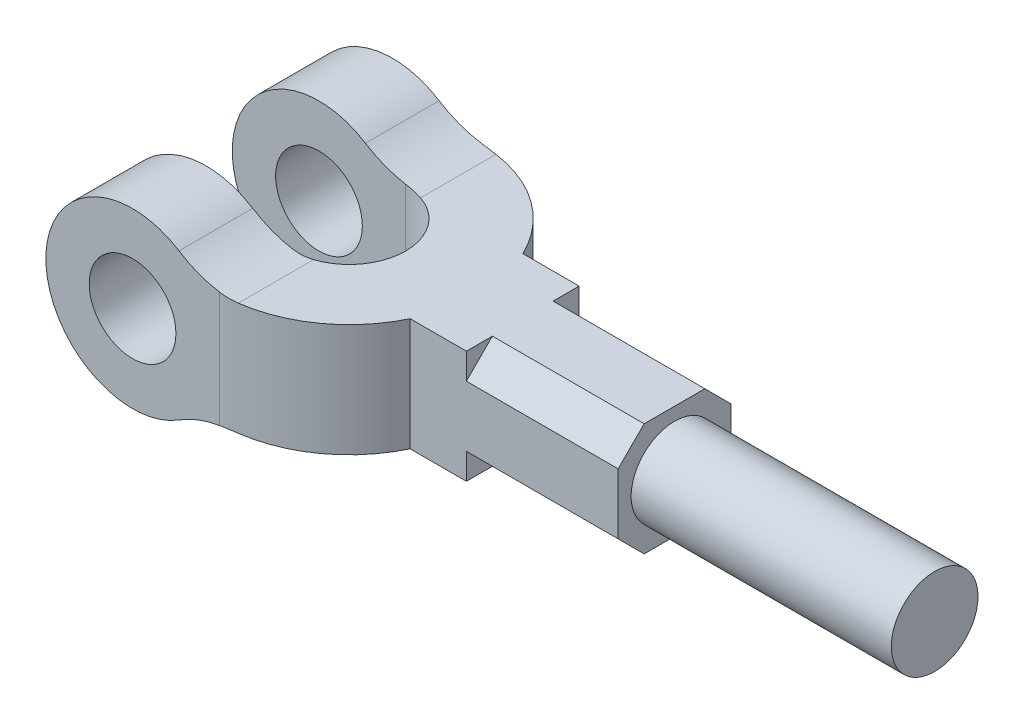
SolidWorks part; units mm, degrees
ref_plane "Front Plane" through (0, 0, 0) normal (0, 0, 1) x (1, 0, 0)
ref_plane "Top Plane" through (0, 0, 0) normal (0, 1, 0) x (1, 0, 0)
ref_plane "Right Plane" through (0, 0, 0) normal (1, 0, 0) x (0, 0, -1)
sketch "Sketch1" plane through (0, 0, 0) normal (0, 1, 0) x (1, 0, 0)
  line L1 (-57.5, 30) -> (57.5, 30)
  line L2 (-57.5, 30) -> (-57.5, -30)
  line L3 (-57.5, -30) -> (57.5, -30)
  line L4 (57.5, 30) -> (57.5, -30)
  line L5 (-57.5, 30) -> (57.5, -30) construction
  line L6 (-57.5, -30) -> (57.5, 30) construction
  point P0 (0, 0)
  dimension "D1" = 60
  dimension "D2" = 115
extrude "Boss-Extrude1" add sketch "Sketch1" along normal blind 40
sketch "Sketch2" plane through (0, 40, 0) normal (0, 1, 0) x (1, 0, 0)
  line L0 (-57.5, 0) -> (15.5, 0) construction
  line L1 (-57.5, 0) -> (52.37, 0) construction
  line L3 (-57.5, 13) -> (-17.5, 13)
  line L6 (-57.5, -30) -> (-17.5, -30)
  line L7 (-57.5, -13) -> (-57.5, -30)
  line L9 (-57.5, 13) -> (52.37, 13) construction
  line L10 (-57.5, 13) -> (-57.5, 30)
  line L11 (-57.5, 30) -> (-17.5, 30)
  line L15 (57.5, 30) -> (-57.5, 30) construction
  line L17 (-57.5, 30) -> (-57.5, -30) construction
  line L18 (-57.5, -13) -> (-17.5, -13)
  line L19 (9.537, -13) -> (57.5, -13)
  line L20 (57.5, -30) -> (57.5, 30) construction
  line L21 (57.5, -13) -> (57.5, 13)
  line L22 (57.5, 13) -> (9.537, 13)
  arc A4 (-17.5, -13) -> (-17.5, 13) centre (-17.5, 0) ccw
  arc A5 (-17.5, -30) -> (9.537, -13) centre (-17.5, 0) ccw
  arc A6 (9.537, 13) -> (-17.5, 30) centre (-17.5, 0) ccw
  line M12 (57.5, -30) -> (57.5, 30)
  line M13 (57.5, 30) -> (-57.5, 30)
  line M14 (-57.5, 30) -> (-57.5, -30)
  line M15 (-57.5, -30) -> (57.5, -30)
  dimension "D4" = 40
  dimension "D3" = 40
  dimension "D1" = 13
  dimension "D2" = 13
extrude "Cut-Extrude1" cut sketch "Sketch2" against normal blind 40 contours L18 A4 L3 M14 | A6 L22 M12 M13 | A5 L19 M15 M12 region at (-32.3111, 40, 0) region at (29.3463, 40, -22.0233) region at (29.3463, 40, 22.0233)
sketch "Sketch3" plane through (0, 0, 30) normal (0, 0, 1) x (1, 0, 0)
  line L0 (57.5, 0) -> (57.5, 40) construction
  line L1 (-57.5, 40) -> (-17.5, 40) construction
  line L2 (-37.5, 20) -> (57.5, 20) construction
  line L3 (-13.3961, 7) -> (57.5, 7)
  line L4 (-13.3961, 33) -> (57.5, 33)
  line L5 (-37.5, 33) -> (57.5, 33) construction
  line L6 (-37.5, 7) -> (57.5, 7) construction
  line L7 (57.5, 33) -> (57.5, 7)
  line L8 (9.537, 0) -> (57.5, 0) construction
  line L9 (-17.5, 0) -> (9.537, 0) construction
  line L10 (-57.5, 0) -> (-17.5, 0) construction
  line L11 (9.537, 40) -> (-17.5, 40) construction
  line L12 (9.537, 40) -> (57.5, 40) construction
  line L13 (9.537, 0) -> (57.5, 0)
  line L14 (-17.5, 0) -> (9.537, 0)
  line L15 (-57.5, 0) -> (-17.5, 0)
  line L16 (-57.5, 40) -> (-17.5, 40)
  line L17 (9.537, 40) -> (-17.5, 40)
  line L18 (9.537, 40) -> (57.5, 40)
  line L19 (57.5, 0) -> (57.5, 40)
  arc A0 (-26.7871, 36.8889) -> (-26.7871, 3.1111) centre (-37.5, 20) ccw
  circle A1 centre (-37.5, 20) radius 10
  arc A2 (-13.3961, 33) -> (-26.7871, 36.8889) centre (-13.3961, 58) cw
  arc A3 (-13.3961, 7) -> (-26.7871, 3.1111) centre (-13.3961, -18) ccw
  line M4 (-57.5, 0) -> (-17.5, 0)
  line M5 (-17.5, 0) -> (-17.5, 40)
  line M6 (-17.5, 40) -> (-57.5, 40)
  line M7 (-57.5, 40) -> (-57.5, 0)
  dimension "D1" = 40
  dimension "D2" = 20
  dimension "D7" = 25
  dimension "D3" = 95
  dimension "D4" = 20
  dimension "D5" = 13
  dimension "D6" = 13
extrude "Cut-Extrude3" cut sketch "Sketch3" against normal blind 98 contours A0 L16 M7 | A0 M7 M4 | A2 A0 M5 M6 | A2 L4 L19 L18 L17 M5 | L3 A3 L14 L13 L19 M5 | A3 A0 L15 M5 region at (20.0322, 3.497, 30) region at (-23.0334, 2.3964, 30) region at (20.0322, 36.503, 30) region at (-23.0334, 37.6036, 30) region at (-53.0326, 4.4674, 30) region at (-53.0326, 35.5326, 30)
extrude "Cut-Extrude4" cut sketch "Sketch3<4>" against normal blind 98 contours A1 region at (-37.5, 20, 30)
sketch "Sketch3<4>" plane through (0, 0, 30) normal (0, 0, 1) x (1, 0, 0) same geometry as "Sketch3"
sketch "Sketch4" plane through (57.5, 0, 0) normal (1, 0, 0) x (0, 0, -1)
  line L0 (13, 7) -> (-13, 7) construction
  line L1 (13, 7) -> (13, 33) construction
  line L2 (-13, 33) -> (-13, 27)
  line L3 (-12.3352, 33) -> (-29.718, 33) construction
  line L4 (13, 33) -> (-13, 33) construction
  line L5 (-13, 7) -> (-13, 33) construction
  line L6 (-13, 33) -> (-7, 33)
  line L7 (-13, 27) -> (-7, 33)
  line L8 (13, 33) -> (7, 33)
  line L9 (13, 33) -> (13, 27)
  line L10 (7, 33) -> (13, 27)
  line L11 (13, 7) -> (13, 13)
  line L12 (13, 7) -> (7, 7)
  line L13 (13, 13) -> (7, 7)
  line L14 (-13, 7) -> (-7, 7)
  line L15 (-13, 7) -> (-13, 13)
  line L16 (-7, 7) -> (-13, 13)
  circle A0 centre (0, 20) radius 10
  point P27 (0, 20)
  dimension "D1" = 20
  dimension "D2" = 13
  dimension "D3" = 13
  dimension "D4" = 6
  dimension "D5" = 6
  dimension "D6" = 4
extrude "Boss-Extrude2" add sketch "Sketch4" along normal blind 60 contours A0 region at (57.5, 20, 0)
extrude "Cut-Extrude5" cut sketch "Sketch4<3>" against normal blind 35
sketch "Sketch4<3>" plane through (57.5, 0, 0) normal (1, 0, 0) x (0, 0, -1) same geometry as "Sketch4"
